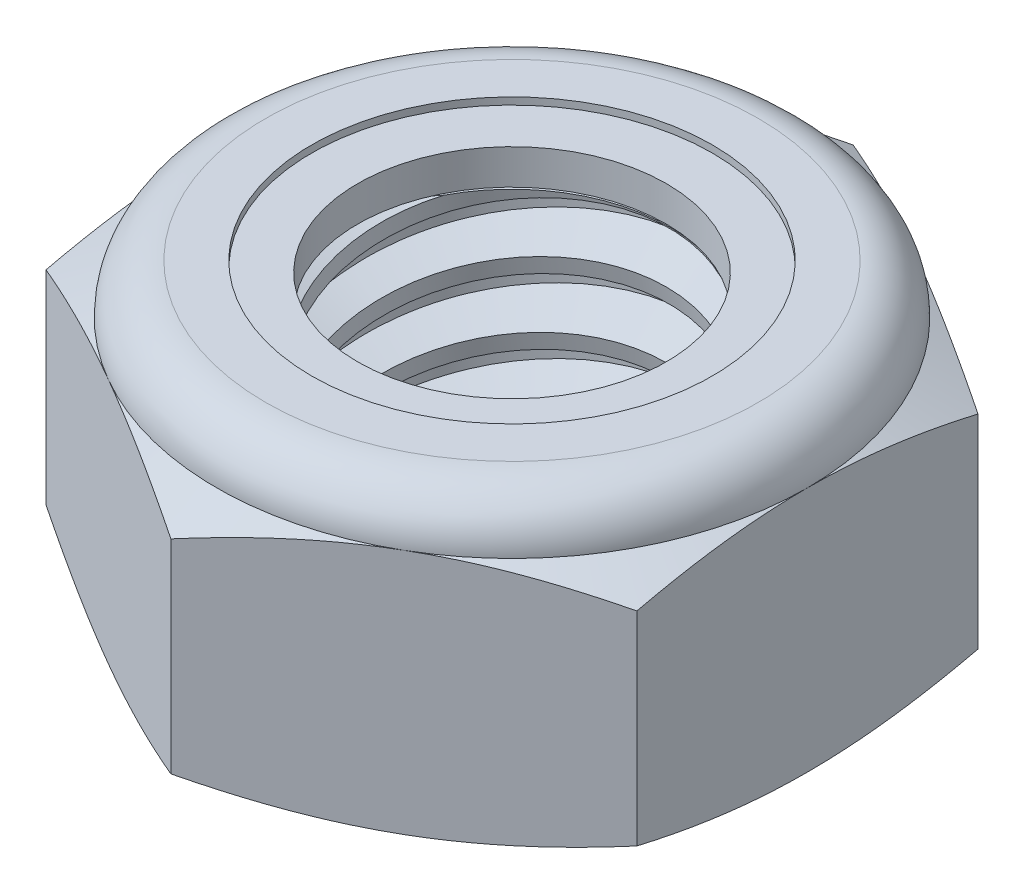
SolidWorks part; units mm, degrees
ref_plane "Front" through (0, 0, 0) normal (0, 0, 1) x (1, 0, 0)
ref_plane "Top" through (0, 0, 0) normal (0, 1, 0) x (1, 0, 0)
ref_plane "Right" through (0, 0, 0) normal (1, 0, 0) x (0, 0, -1)
sketch "Sketch1" plane through (0, 0, 0) normal (0, 1, 0) x (1, 0, 0)
  line L1 (0, 7.3323) -> (-6.35, 3.6662)
  line L2 (-6.35, 3.6662) -> (-6.35, -3.6662)
  line L3 (-6.35, -3.6662) -> (0, -7.3323)
  line L4 (0, -7.3323) -> (6.35, -3.6662)
  line L5 (6.35, -3.6662) -> (6.35, 3.6662)
  line L6 (6.35, 3.6662) -> (0, 7.3323)
  circle A0 centre (0, 0) radius 6.35 construction
  dimension "Hex Flats" = 12.7
extrude "Extrude1" add sketch "Sketch1" along normal blind 6.35
sketch "Sketch2" plane through (0, 0, 0) normal (1, 0, 0) x (0, 0, -1)
  line L0 (-3.9624, 0) -> (-3.9624, 6.35) construction
  line L1 (0, 0) -> (3.9624, 0)
  line L2 (0, 0) -> (0, 6.35)
  line L3 (0, 6.35) -> (3.9624, 6.35)
  line L4 (3.9624, 0) -> (3.9624, 6.35)
  line L5 (-3.6662, 6.35) -> (3.6662, 6.35) construction
  line L7 (0, -3.9624) -> (0, 0) construction
  dimension "Thread Dia" = 7.9248
revolve "Revolve1" add sketch "Sketch2" angle 360 about L7
sketch "Sketch3" plane through (0, 0, 0) normal (1, 0, 0) x (0, 0, -1)
  line L0 (3.9624, 6.35) -> (-3.9624, 6.35) construction
  line L1 (-3.9624, 6.35) -> (-3.9624, 4.9389) construction
  line L2 (-3.9624, 4.9389) -> (3.9624, 6.35) construction
  line L3 (3.9624, 6.35) -> (3.9933, 6.1763) construction
  line L4 (3.9933, 6.1763) -> (4.2098, 4.9607)
  line L5 (4.2098, 4.9607) -> (3.3805, 5.261)
  line L6 (3.3805, 5.261) -> (3.3187, 5.6083)
  line L7 (3.3187, 5.6083) -> (3.9933, 6.1763)
  line L8 (3.3496, 5.4346) -> (4.1015, 5.5685) construction
  line L9 (3.9624, 6.35) -> (3.9624, 5.5438) construction
  line L10 (3.9624, 5.5438) -> (-3.9624, 4.1327) construction
  line L11 (-3.9624, 4.1327) -> (-3.9624, 4.9389) construction
  line L12 (-0.2692, 6.35) -> (0.2692, 3.3264) construction
  line L13 (-3.9624, 0) -> (-3.9624, 6.35) construction
  line L14 (0, 6.35) -> (3.9624, 6.35) construction
  line L15 (3.9624, 0) -> (3.9624, 6.35) construction
  point P13 (0, 4.8382)
  dimension "D1" = 0.1764
  dimension "D2" = 0.3528
  dimension "Thread Pitch" = 1.4111
  dimension "D4" = 60
  dimension "D5" = 1.4111
revolve "Cut-Revolve1" cut sketch "Sketch3" angle 360 about L12
pattern_linear "LPattern1" count 5 spacing 1.4111 along (0, -1, 0) count 2 spacing 1.4111 along (0, 1, 0) of "Cut-Revolve1"
sketch "Sketch4" plane through (0, 0, 0) normal (1, 0, 0) x (0, 0, -1)
  line L0 (0, 6.35) -> (3.9624, 6.35)
  line L1 (3.9624, 6.35) -> (3.3187, 6.0498)
  line L2 (3.3187, 6.0498) -> (3.3187, 0.3002)
  line L3 (3.3187, 0.3002) -> (3.9624, 0)
  line L4 (3.9624, 0) -> (0, 0)
  line L5 (0, 0) -> (0, 6.35)
  line L6 (3.9624, 0) -> (3.9624, 6.35) construction
  line L7 (0, 6.35) -> (3.9624, 6.35) construction
  line L8 (0, 0) -> (3.9624, 0) construction
  line L9 (0, 0) -> (0, 6.35) construction
  line L10 (0, 6.35) -> (0, 7.0603) construction
  dimension "D1" = 25
revolve "Cut-Revolve2" cut sketch "Sketch4" angle 360 about L10
combine bodies "Combine1" operation type subtract main body 112 bodies to subtract 111
sketch "Sketch5" plane through (0, 0, 0) normal (1, 0, 0) x (0, 0, -1)
  line L0 (0, 0) -> (6.35, 0)
  line L1 (6.35, 0) -> (7.3323, 0.4581)
  line L2 (7.3323, 0.4581) -> (7.3323, 4.8336)
  line L3 (7.3323, 4.8336) -> (6.35, 5.2917)
  line L4 (5.2917, 6.35) -> (5.2917, 7.62)
  line L5 (5.2917, 7.62) -> (8.6023, 7.62)
  line L6 (8.6023, 7.62) -> (8.6023, -1.27)
  line L7 (8.6023, -1.27) -> (0, -1.27)
  line L8 (0, -1.27) -> (0, 0)
  line L9 (6.35, 5.2917) -> (6.35, 0) construction
  line L10 (0, 0) -> (3.9624, 0) construction
  line L13 (7.3323, 2.6458) -> (8.6023, 2.6458) construction
  line L14 (7.3323, 6.35) -> (7.3323, 0) construction
  line L15 (0, 0) -> (0, 7.62) construction
  line L20 (0, 7.62) -> (5.2917, 7.62) construction
  line L22 (0, 6.35) -> (3.9624, 6.35) construction
  arc A0 (6.35, 5.2917) -> (5.2917, 6.35) centre (5.2917, 5.2917) ccw
  dimension "D1" = 25
  dimension "D2" = 1.27
  dimension "D3" = 6.35
  dimension "D4" = 1.0583
revolve "Cut-Revolve3" cut sketch "Sketch5" angle 360 about L15
sketch "Sketch6" plane through (0, 0, 0) normal (1, 0, 0) x (0, 0, -1)
  line L0 (0, 5.2917) -> (6.1976, 5.2917)
  line L1 (5.2917, 6.1976) -> (4.3052, 6.1976)
  line L2 (0, 7.62) -> (0, 5.2917)
  line L3 (4.3052, 7.62) -> (0, 7.62)
  line L4 (0, 7.62) -> (5.2917, 7.62) construction
  line L5 (0, 0) -> (0, 7.62) construction
  line L6 (0, 7.62) -> (0, 44.323) construction
  line L7 (4.3052, 6.1976) -> (4.3052, 7.62)
  line L8 (5.2917, 6.35) -> (5.2917, 6.1976) construction
  line L9 (4.3052, 6.1976) -> (3.3187, 6.1976) construction
  line L10 (3.3187, 6.1976) -> (3.3187, 6.0498) construction
  arc A0 (6.1976, 5.2917) -> (5.2917, 6.1976) centre (5.2917, 5.2917) ccw
  arc A1 (6.35, 5.2917) -> (5.2917, 6.35) centre (5.2917, 5.2917) ccw construction
  dimension "D1" = 0.1524
revolve "Cut-Revolve4" cut sketch "Sketch6" angle 360 about L6
sketch "Sketch7" plane through (0, 0, 0) normal (1, 0, 0) x (0, 0, -1)
  line L0 (3.3187, 5.3679) -> (6.1179, 5.3679)
  line L1 (5.2917, 6.1214) -> (3.3187, 6.1214)
  line L2 (3.3187, 6.1214) -> (3.3187, 5.3679)
  line L3 (3.3187, 5.3679) -> (0, 5.3679) construction
  line L4 (0, 5.3679) -> (0, 6.1214) construction
  line L5 (0, 6.1214) -> (3.3187, 6.1214) construction
  line L6 (3.3187, 5.3679) -> (3.3187, 5.2917) construction
  line L7 (0, 5.2917) -> (6.1976, 5.2917) construction
  line L8 (5.2917, 6.1214) -> (5.2917, 6.1976) construction
  arc A0 (6.1179, 5.3679) -> (5.2917, 6.1214) centre (5.2917, 5.2917) ccw
  arc A2 (6.1976, 5.2917) -> (5.2917, 6.1976) centre (5.2917, 5.2917) ccw construction
  dimension "D1" = 0.0762
revolve "Revolve2" add sketch "Sketch7" angle 360 about L4
equation "\"D1@Sketch3\"=\"Thread Pitch@Sketch3\"/8"
equation "\"D2@Sketch3\"=\"Thread Pitch@Sketch3\"/4"
equation "\"D5@Sketch3\"=\"Thread Pitch@Sketch3\""
equation "\"D4@LPattern1\"=\"Thread Pitch@Sketch3\""
equation "\"D3@LPattern1\"=\"Thread Pitch@Sketch3\""
equation "\"D1@LPattern1\"=\"Height@Extrude1\"/\"Thread Pitch@Sketch3\""
equation "\"D4@Sketch5\"=\"Height@Extrude1\"/6"
